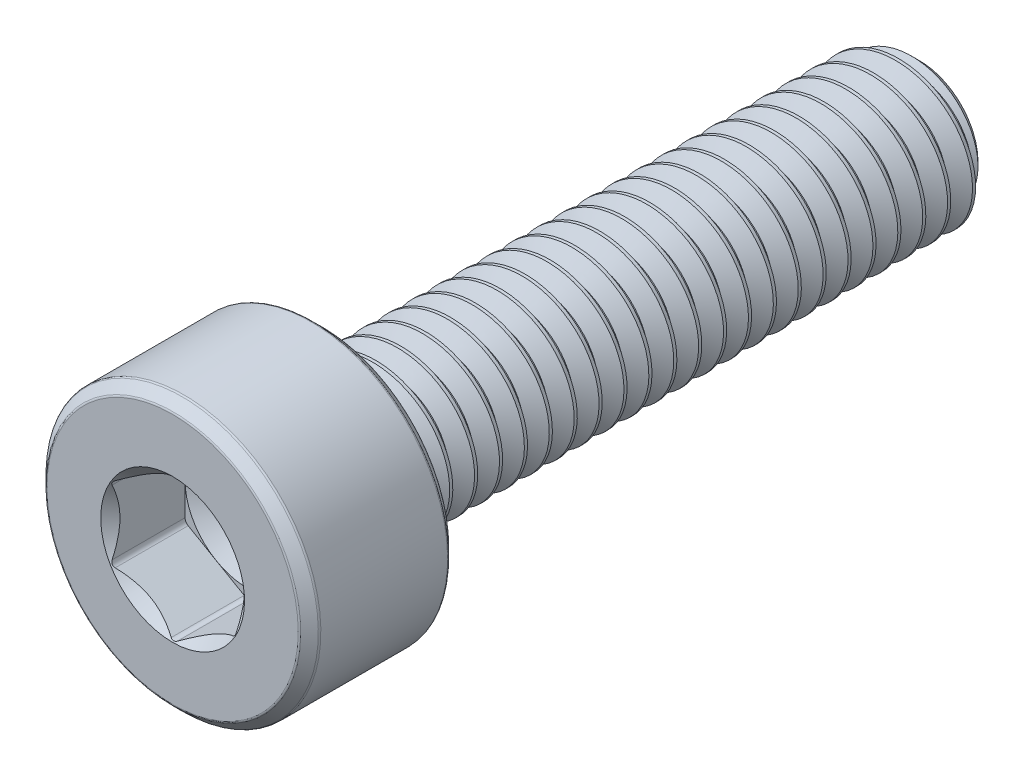
SolidWorks part; units mm, degrees
ref_plane "Front Plane" through (0, 0, 0) normal (0, 0, 1) x (1, 0, 0)
ref_plane "Top Plane" through (0, 0, 0) normal (0, 1, 0) x (1, 0, 0)
ref_plane "Right Plane" through (0, 0, 0) normal (1, 0, 0) x (0, 0, -1)
sketch "Sketch1" plane through (0, 0, 0) normal (1, 0, 0) x (0, 0, -1)
  line L0 (-7.5, 0) -> (7.5, 0) construction
  line L1 (-7.5, 0) -> (-7.5, 2.75)
  line L2 (-7.5, 2.75) -> (-4.5, 2.75)
  line L3 (-4.5, 2.75) -> (-4.5, 1.5)
  line L4 (-4.5, 1.5) -> (7.1752, 1.5)
  line L5 (7.4687, 1.5541) -> (7.7187, 1.1211) construction
  line L6 (7.7187, 1.1211) -> (7.9687, 1.5541) construction
  line L7 (7.9687, 1.5541) -> (7.4687, 1.5541) construction
  line L8 (7.1752, 1.5) -> (7.5, 1.1752)
  line L9 (7.5, 1.1752) -> (7.5, 0)
  line L10 (7.5, 1.5) -> (7.9375, 1.5) construction
  line L11 (7.7187, 1.5541) -> (7.7187, 1.5) construction
  line L12 (7.7187, 1.5) -> (7.7187, 1.1752) construction
  line L13 (7.7187, 1.1752) -> (7.7187, 1.1211) construction
  line L14 (7.6875, 1.1752) -> (7.75, 1.1752)
  line L15 (7.4844, 1.5271) -> (7.9531, 1.5271)
  line L16 (7.75, 1.1752) -> (7.9531, 1.5271)
  line L17 (7.6875, 1.1752) -> (7.4844, 1.5271)
  line L18 (-7.5, 1.25) -> (-6, 1.25)
  line L19 (-6, 1.25) -> (-6, 0)
  line L20 (5.75, 1.5) -> (5.75, -1.5) construction
  point P20 (7.7187, 1.5271)
  point P22 (5.75, -1.5)
  point P28 (5.75, 0)
  point P29 (7.1752, -1.5)
  dimension "Head Diameter" = 5.5
  dimension "Length" = 12
  dimension "Head Height" = 3
  dimension "Thread Size" = 3
  dimension "D1" = 45
  dimension "Thread Pitch" = 0.5
  dimension "D3" = 0.0625
  dimension "Drive Size" = 2.5
  dimension "D4" = 1.75
  dimension "D5" = 1.5
sketch "Sketch3" plane through (0, 0, 0) normal (1, 0, 0) x (0, 0, -1)
  line L0 (-7.5, 2.5224) -> (-7.5, 1.25)
  line L1 (-7.5, 1.25) -> (-6, 1.25)
  line L2 (-6, 1.25) -> (-6, 0)
  line L3 (-6, 0) -> (7.5, 0)
  line L4 (7.5, 0) -> (7.5, 1.1752)
  line L5 (7.5, 1.1752) -> (7.1752, 1.5)
  line L6 (7.1752, 1.5) -> (-4.5, 1.5)
  line L7 (-4.5, 1.5) -> (-4.5, 2.5224)
  line L8 (-4.7276, 2.75) -> (-7.2724, 2.75)
  line L9 (-7.4849, 2.5589) -> (-7.3089, 2.7349)
  line L11 (-7.5, 2.75) -> (-4.5, 2.75) construction
  line L12 (-4.6911, 2.7349) -> (-4.5151, 2.5589)
  arc A5 (-4.5151, 2.5589) -> (-4.5, 2.5224) centre (-4.5516, 2.5224) cw
  arc A6 (-4.7276, 2.75) -> (-4.6911, 2.7349) centre (-4.7276, 2.6984) cw
  arc A7 (-7.2724, 2.75) -> (-7.3089, 2.7349) centre (-7.2724, 2.6984) ccw
  arc A8 (-7.5, 2.5224) -> (-7.4849, 2.5589) centre (-7.4484, 2.5224) cw
  point P17 (-6, 2.75)
  point P29 (-7.5, 2.5438)
  dimension "D3" = 0.0516
  dimension "D1" = 45
  dimension "D2" = 0.2062
revolve "Revolve1" add sketch "Sketch3" angle 360 about L0
sketch "Sketch4" plane through (0, 0, 7.5) normal (0, 0, 1) x (1, 0, 0)
  line L1 (0, 1.4434) -> (-1.25, 0.7217)
  line L2 (-1.25, 0.7217) -> (-1.25, -0.7217)
  line L3 (-1.25, -0.7217) -> (0, -1.4434)
  line L4 (0, -1.4434) -> (1.25, -0.7217)
  line L5 (1.25, -0.7217) -> (1.25, 0.7217)
  line L6 (1.25, 0.7217) -> (0, 1.4434)
  circle A0 centre (0, 0) radius 1.25 construction
extrude "Cut-Extrude1" cut sketch "Sketch4" against normal up to vertex (1.5 mm away) up to point (0, 1.25, 6)
sketch "Sketch5" plane through (0, 0, 7.5) normal (0, 0, 1) x (1, 0, 0)
  circle A0 centre (0, 0) radius 1.4434
extrude "Cut-Extrude2" cut sketch "Sketch5" against normal up to next (1.5 mm away) draft 45
sketch "Sketch10" plane through (0, 0, 6) normal (0, 0, 1) x (1, 0, 0)
  line L0 (1.25, 0.7217) -> (1.25, -0.7217) construction
  circle A0 centre (0, 0) radius 1.25
extrude "Cut-Extrude3" cut sketch "Sketch10" against normal through all draft 60
fillet "Fillet1" radius 0.125 6 edges at (-1.25, 0.7217, 6.75) (0, 1.4434, 6.75) (1.25, 0.7217, 6.75) (1.25, -0.7217, 6.75) (0, -1.4434, 6.75) (-1.25, -0.7217, 6.75)
sketch "Sketch6" plane through (0, 0, -7.5) normal (0, 0, -1) x (-1, 0, 0)
  circle A0 centre (0, 0) radius 1.5 construction
  circle A1 centre (0, 0) radius 1.5
curve "Helix/Spiral1" pitch 0.5 height 12.5 radius 1.5 centre (0, 0, -7.5) axis (0, 0, 1) start towards (0, 1, 0)
sketch "Sketch7" plane through (0, 0, 0) normal (1, 0, 0) x (0, 0, -1)
  line L0 (7.6875, 1.1752) -> (7.75, 1.1752) construction
  line L1 (7.6875, 1.1752) -> (7.4844, 1.5271) construction
  line L2 (7.4844, 1.5271) -> (7.9531, 1.5271) construction
  line L3 (7.75, 1.1752) -> (7.9531, 1.5271) construction
  line L4 (7.6875, 1.1752) -> (7.75, 1.1752)
  line L5 (7.6875, 1.1752) -> (7.4844, 1.5271)
  line L6 (7.4844, 1.5271) -> (7.9531, 1.5271)
  line L7 (7.75, 1.1752) -> (7.9531, 1.5271)
sweep "Cut-Sweep1" cut profiles "Sketch7" path "Helix/Spiral1" align with end faces yes
sketch "Sketch11" plane through (0, 0, 0) normal (1, 0, 0) x (0, 0, -1)
  line L0 (-4.5, 1.625) -> (-4.375, 1.5) construction
  line L1 (-4.5, 2.75) -> (-4.5, 1.5) construction
  line L2 (-4.5, 1.5) -> (7.1752, 1.5) construction
  line L3 (-4.375, 1.5) -> (-4.25, 1.5)
  line L4 (-4.25, 1.5) -> (-2.75, 0)
  line L5 (-7.5, 0) -> (7.5, 0) construction
  line L6 (-2.75, 0) -> (-4.5, 0)
  line L7 (-4.5, 0) -> (-4.5, 1.625) construction
  line L8 (-4.5, 1.625) -> (-5.2783, 1.625)
  line L9 (-5.2783, 1.625) -> (-5.2783, 0)
  line L10 (-5.2783, 0) -> (-4.5, 0)
  arc A0 (-4.375, 1.5) -> (-4.5, 1.625) centre (-4.375, 1.625) cw
  dimension "D1" = 45
  dimension "D2" = 0.125
  dimension "D3" = 45
  dimension "D4" = 0.25
revolve "Revolve2" add sketch "Sketch11" angle 360 about L6
equation "\"D3@Sketch1\" = \"Thread Pitch@Sketch1\" / 8"
equation "\"D4@Sketch1\" = \"Thread Pitch@Sketch1\" * 3.5"
equation "\"D3@Helix/Spiral1\" = \"Length@Sketch1\" + \"Thread Pitch@Sketch1\""
equation "\"D4@Helix/Spiral1\" = \"Thread Pitch@Sketch1\""
equation "\"D5@Sketch1\"=\"Head Height@Sketch1\"*0.5"
equation "\"D2@Sketch3\"=\"Head Diameter@Sketch1\" *0.0375"
equation "\"D2@Sketch11\"=\"Thread Pitch@Sketch1\" / 4"
equation "\"D4@Sketch11\"=\"Thread Pitch@Sketch1\"/2"
equation "\"D1@Fillet1\"=\"Drive Size@Sketch1\"*0.05"
equation "\"D1@Fillet1\" = \"Drive Size@Sketch1\" * 0.05"
equation "\"D3@Sketch3\"=\"D2@Sketch3\"*0.25"
